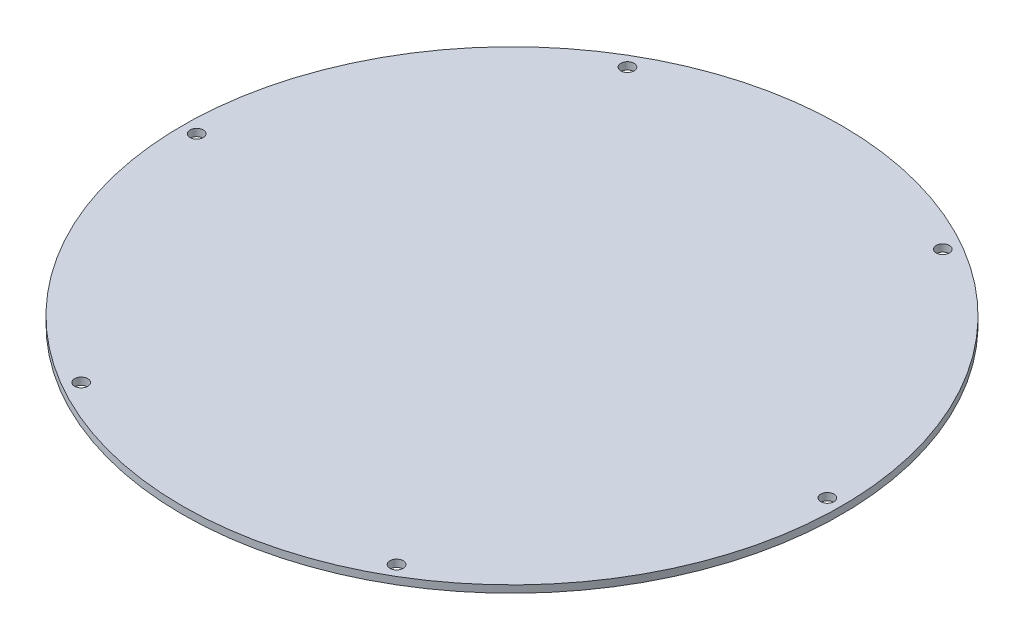
SolidWorks part; units mm, degrees
ref_plane "Front Plane" through (0, 0, 0) normal (0, 0, 1) x (1, 0, 0)
ref_plane "Top Plane" through (0, 0, 0) normal (0, 1, 0) x (1, 0, 0)
ref_plane "Right Plane" through (0, 0, 0) normal (1, 0, 0) x (0, 0, -1)
sketch "Sketch1" plane through (0, 0, 0) normal (0, 1, 0) x (1, 0, 0)
  circle A0 centre (0, 0) radius 50 construction
  circle A1 centre (0, 0) radius 52.25
  point P5 (25, -43.3013)
  point P6 (50, 0)
  point P9 (-25, -43.3013)
  point P10 (-50, 0)
  point P11 (-25, 43.3013)
  point P12 (25, 43.3013)
  point P13 (0, 0)
  dimension "D1" = 100
  dimension "D2" = 2.25
  dimension "D3" = 6
base flange "Base-Flange4" sketch "Sketch1" thickness 1.15 reverse thickness direction yes parameters "D1"=0.7366
hole_wizard "Ø2.1 (2.1) Diameter Hole2" positions "Sketch29" profile "Sketch30" hole size "Ø2.1" standard "ISO" end condition through all
sketch "Sketch29" plane through (0, 0, 0) normal (0, -1, 0) x (-1, 0, 0)
  point P0 (50, 0)
  point P3 (25, -43.3013)
  point P6 (-25, -43.3013)
  point P9 (-50, 0)
  point P12 (-25, 43.3013)
  point P15 (25, 43.3013)
sketch "Sketch30" plane through (-50, 0, 0) normal (1, 0, 0) x (0, 0, -1)
  line L0 (0, 0) -> (0, 1.15)
  line L1 (0, 1.15) -> (1.05, 1.15)
  line L2 (1.05, 1.15) -> (1.05, 0)
  line L5 (1.05, 0) -> (0, 0)
  line L11 (0, -6.35) -> (0, 107.95) construction
  dimension "Thru Hole Dia." = 2.1
  dimension "Thru Hole Depth" = 1.15
sketch "Bend-Lines7" [suppressed] plane through (0, 0, 0) normal (0, 1, 0) x (1, 0, 0)
sketch "Bounding-Box7" [suppressed] plane through (0, 0, 0) normal (0, 1, 0) x (1, 0, 0)
sheet metal parameters "Sheet-Metal5" thickness 1.15 parameters "D1"=0.7366
flat pattern "Flat-Pattern5" [suppressed]
sketch "Bend-Lines8" plane through (0, 0, 0) normal (0, 1, 0) x (1, 0, 0)
sketch3d "Bounding-Box8" [suppressed]
  line L0 (52.2777, 52.2223, 0) -> (52.2223, -52.2777, 0) construction
  line L1 (-52.2223, 52.2777, 0) -> (-52.2777, -52.2223, 0) construction
  line L2 (52.2777, 52.2223, 0) -> (-52.2223, 52.2777, 0) construction
  line L3 (52.2223, -52.2777, 0) -> (-52.2777, -52.2223, 0) construction
sheet metal parameters "Sheet-Metal6" thickness 1.15 parameters "D1"=0.7366
flat pattern "Flat-Pattern5"
sketch "Bend-Lines8" plane through (0, 0, 0) normal (0, 1, 0) x (1, 0, 0)
sketch3d "Bounding-Box8" [suppressed]
  line L0 (52.2777, 52.2223, 0) -> (52.2223, -52.2777, 0) construction
  line L1 (-52.2223, 52.2777, 0) -> (-52.2777, -52.2223, 0) construction
  line L2 (52.2777, 52.2223, 0) -> (-52.2223, 52.2777, 0) construction
  line L3 (52.2223, -52.2777, 0) -> (-52.2777, -52.2223, 0) construction
